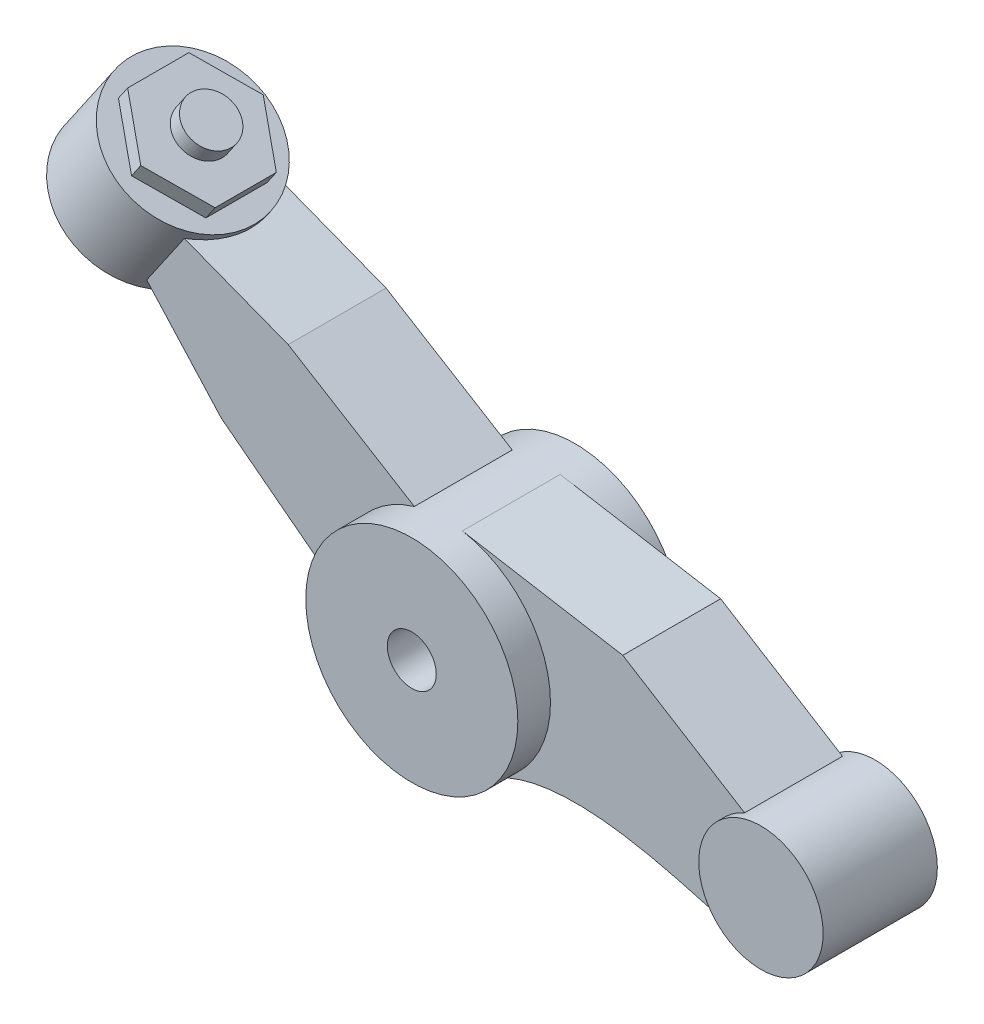
SolidWorks part; units mm, degrees
ref_plane "Front Plane" through (0, 0, 0) normal (0, 0, 1) x (1, 0, 0)
ref_plane "Top Plane" through (0, 0, 0) normal (0, 1, 0) x (1, 0, 0)
ref_plane "Right Plane" through (0, 0, 0) normal (1, 0, 0) x (0, 0, -1)
sketch "Sketch1" plane through (0, 0, 0) normal (0, 0, 1) x (1, 0, 0)
  line L0 (0, 2.0366) -> (0, -2.3554) construction
  line L1 (-3.8115, 0) -> (3.3962, 0) construction
  line L2 (0, 0) -> (-3.6604, 2.5129) construction
  line L4 (0.2195, 1.2813) -> (2.186, 0.9445)
  line L5 (2.186, 0.9445) -> (3.6798, 0.0189)
  line L6 (-3.4694, 2.7912) -> (-3.8515, 2.2347)
  line L7 (-3.4694, 2.7912) -> (-1.9154, 2.1922)
  line L8 (-1.9154, 2.1922) -> (-0.3688, 1.2466)
  line L9 (-2.7341, 0.9997) -> (-1.2958, -0.1038)
  line L10 (-3.8515, 2.2347) -> (-2.7341, 0.9997)
  circle A0 centre (0, 0) radius 0.3
  circle A1 centre (0, 0) radius 1.3
  circle A2 centre (3.98, -0.682) radius 0.7625
  spline S0 degree 3 poles (3.4947, -1.2701) (2.8192, -1.0862) (1.8304, -0.7824) (0.8742, -0.9984) (0.6426, -1.1301) knots 0 0 0 0 0.738093 1 1 1 1
  dimension "D1" = 2.6
  dimension "D2" = 0.6
  dimension "D3" = 1.525
  dimension "D4" = 0.682
  dimension "D5" = 3.98
  dimension "D6" = 4.44
  dimension "D7" = 0.675
  dimension "D8" = 0.819
  dimension "D9" = 34.47
extrude "Boss-Extrude1" add sketch "Sketch1" along normal mid plane 2 contours A1 A0 region at (0.9657, 0.8144, 0)
extrude "Boss-Extrude2" add sketch "Sketch1<3>" along normal mid plane 1.4 separate body contours A2 region at (3.98, -0.682, 0)
sketch "Sketch1<3>" plane through (0, 0, 0) normal (0, 0, 1) x (1, 0, 0) same geometry as "Sketch1"
extrude "Boss-Extrude3" add sketch "Sketch1<4>" along normal mid plane 1.2 contours S0 A2 L5 L4 A1 | A1 L8 L7 L6 L10 L9 region at (2.164, -0.0535, 0) region at (-2.166, 1.487, 0)
sketch "Sketch1<4>" plane through (0, 0, 0) normal (0, 0, 1) x (1, 0, 0) same geometry as "Sketch1"
sketch "Sketch2" plane through (0, 0, 0) normal (0, 0, 1) x (1, 0, 0)
  line L0 (-3.8515, 2.2347) -> (-3.444, 2.8283)
  line L1 (-3.444, 2.8283) -> (-3.7696, 3.0518)
  line L2 (-3.7696, 3.0518) -> (-4.8331, 1.5026)
  line L3 (-4.303, 1.9019) -> (-3.8515, 2.2347)
  line L4 (-3.4694, 2.7912) -> (-3.8515, 2.2347) construction
  arc A0 (-4.8331, 1.5026) -> (-4.303, 1.9019) centre (-4.6351, 1.7912) ccw
  point P9 (-3.4252, 2.8555)
  dimension "D1" = 0.72
  dimension "D3" = 0.35
  dimension "D2" = 0.395
  dimension "D4" = 1
revolve "Revolve1" add sketch "Sketch2" angle 360 about L2
sketch "Sketch3" plane through (0, 0, 0) normal (0, 0, 1) x (1, 0, 0)
  line L0 (-4.294, 2.288) -> (-3.685, 3.1751)
  line L1 (-3.685, 3.1751) -> (-4.4377, 3.6918)
  line L2 (-4.4377, 3.6918) -> (-5.0467, 2.8047)
  line L3 (-5.0467, 2.8047) -> (-4.294, 2.288)
  line L5 (-4.5027, 2.6818) -> (-3.8515, 2.2347) construction
  point P2 (-4.1771, 2.4582)
  point P5 (0, 0)
  dimension "D1" = 1.076
  dimension "D2" = 0.913
revolve "Revolve2" add sketch "Sketch3" angle 360 about L0
sketch "Sketch4" plane through (0.3011, 0.4386, 0) normal (0.566, 0.8244, 0) x (0.8244, -0.566, 0)
  line L1 (-4.185, 0.3753) -> (-4.835, 0.7506)
  line L2 (-4.835, 0.7506) -> (-5.485, 0.3753)
  line L3 (-5.485, 0.3753) -> (-5.485, -0.3753)
  line L4 (-5.485, -0.3753) -> (-4.835, -0.7506)
  line L5 (-4.835, -0.7506) -> (-4.185, -0.3753)
  line L6 (-4.185, -0.3753) -> (-4.185, 0.3753)
  circle A0 centre (-4.835, 0) radius 0.65 construction
  dimension "D1" = 1.3
extrude "Boss-Extrude4" add sketch "Sketch4" along normal mid plane 0.4
sketch "Sketch5" plane through (0.4143, 0.6035, 0) normal (0.566, 0.8244, 0) x (0.8244, -0.566, 0)
  circle A0 centre (-4.835, 0) radius 0.3
  dimension "D1" = 0.6
extrude "Boss-Extrude5" add sketch "Sketch5" along normal mid plane 0.4
